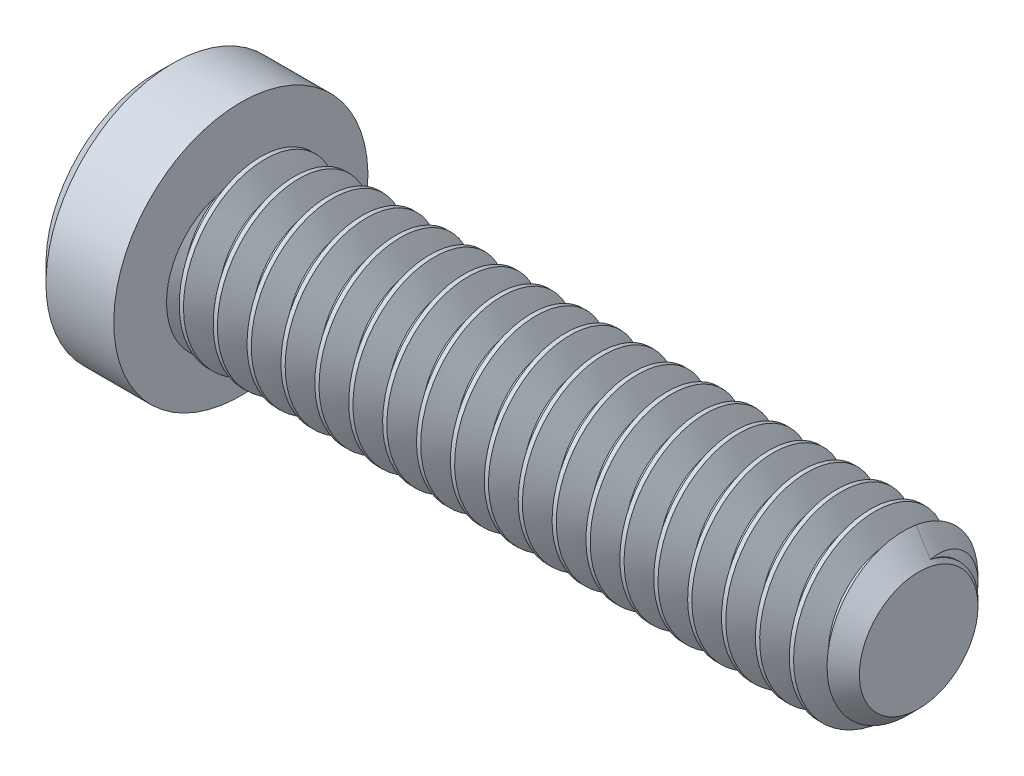
SolidWorks part; units mm, degrees
ref_plane "Front Plane" through (0, 0, 0) normal (0, 0, 1) x (1, 0, 0)
ref_plane "Top Plane" through (0, 0, 0) normal (0, 1, 0) x (1, 0, 0)
ref_plane "Right Plane" through (0, 0, 0) normal (1, 0, 0) x (0, 0, -1)
sketch "Sketch1" plane through (0, 0, 0) normal (0, 0, 1) x (1, 0, 0)
  line L0 (12.7, 0) -> (-12.7, 0) construction
  line L1 (12.7, 3.175) -> (12.7, -3.175) construction
  line L2 (-12.7, 4.7625) -> (-12.7, -4.7625) construction
  line L3 (-12.7, 4.7625) -> (-15.24, 4.7625) construction
  line L4 (-15.24, 4.7625) -> (-15.875, 4.1275) construction
  line L5 (-15.875, 4.1275) -> (-15.875, -4.1275) construction
  line L6 (-15.875, -4.1275) -> (-15.24, -4.7625) construction
  line L7 (-15.24, -4.7625) -> (-12.7, -4.7625) construction
  point P7 (-13.4874, 0)
  point P12 (7.62, -3.175)
  dimension "D1" = 45
  dimension "D2" = 5.08
  dimension "Dec." = 6.35
  dimension "Length" = 25.4
  dimension "Head Dia" = 9.525
  dimension "Head Height" = 3.175
  dimension "Hex Depth" = 2.3876
  dimension "Chamfer" = 0.635
ref_plane "Plane1" through (12.7, 0, 0) normal (1, 0, 0) x (0, 0, -1)
ref_plane "Plane2" through (-15.875, 0, 0) normal (1, 0, 0) x (0, 0, -1)
sketch "Sketch2" plane through (12.7, 0, 0) normal (1, 0, 0) x (0, 0, -1)
  circle A0 centre (0, 0) radius 3.175
extrude "Boss-Extrude1" add sketch "Sketch2" against normal up to vertex (25.4 mm away) up to point (-12.7, 0, 0)
sketch "Sketch3" plane through (12.7, 0, 0) normal (1, 0, 0) x (0, 0, -1)
  circle A0 centre (0, 0) radius 3.175 construction
  circle A1 centre (0, 0) radius 3.175
curve "Helix/Spiral1" pitch 1.27 height 26.67 turns 21 parameters "Pitch"=1.27
chamfer "Chamfer1" distance 0.9525 angle 45 1 edges at (12.7, 0, -3.175)
sketch "Sketch5" plane through (0, 0, 0) normal (0, 0, 1) x (1, 0, 0)
  line L0 (12.1444, 3.175) -> (13.2556, 3.175)
  line L1 (13.2556, 3.175) -> (12.7794, 2.3501)
  line L2 (12.7794, 2.3501) -> (12.6206, 2.3501)
  line L3 (12.6206, 2.3501) -> (12.1444, 3.175)
  line L4 (12.7, 2.3501) -> (12.7, 3.175) construction
  line L5 (12.3825, 2.7626) -> (13.0175, 2.7626) construction
  dimension "D1" = 60
  dimension "D2" = 0.635
  dimension "D3" = 0.1588
sweep "Cut-Sweep1" cut profiles "Sketch5" path "Helix/Spiral1" align with end faces yes
sketch "Sketch4" plane through (-15.875, 0, 0) normal (1, 0, 0) x (0, 0, -1)
  line L0 (-4.7625, 0.7937) -> (4.7625, 0.7937) construction
  line L1 (0, 1.8331) -> (-1.5875, 0.9165)
  line L2 (-1.5875, 0.9165) -> (-1.5875, -0.9165)
  line L3 (-1.5875, -0.9165) -> (0, -1.8331)
  line L4 (0, -1.8331) -> (1.5875, -0.9165)
  line L5 (1.5875, -0.9165) -> (1.5875, 0.9165)
  line L6 (1.5875, 0.9165) -> (0, 1.8331)
  line L7 (0, 0) -> (0, 0.7937) construction
  circle A0 centre (0, 0) radius 1.5875 construction
  dimension "D1" = 9.525
  dimension "Hex Size" = 3.175
  dimension "D2" = 0.7937
sketch "Sketch6" plane through (0, 0, 0) normal (0, 0, 1) x (1, 0, 0)
  line L0 (-15.24, 4.7625) -> (-15.875, 4.1275) construction
  line L1 (-12.7, 4.7625) -> (-15.24, 4.7625) construction
  line L2 (-12.7, 4.7625) -> (-12.7, -4.7625) construction
  line L3 (-15.875, 4.1275) -> (-15.875, -4.1275) construction
  line L4 (-15.24, 4.7625) -> (-15.875, 4.1275)
  line L5 (-12.7, 4.7625) -> (-15.24, 4.7625)
  line L6 (-12.7, 4.7625) -> (-12.7, 0)
  line L7 (-15.875, 4.1275) -> (-15.875, 0)
  line L8 (-12.7, 0) -> (-15.875, 0) construction
  line L9 (-12.7, 0) -> (-15.875, 0)
revolve "Revolve1" add sketch "Sketch6" angle 360 about L8
extrude "Cut-Extrude1" cut sketch "Sketch4" along normal up to vertex (2.3876 mm away) up to point (-13.4874, 0, 0)
sketch "Sketch8" plane through (-15.875, 0, 0) normal (-1, 0, 0) x (0, 0, 1)
  circle A1 centre (0, 0) radius 1.8331
extrude "Cut-Extrude2" cut sketch "Sketch8" against normal through all draft 45
equation "\"D3@Helix/Spiral1\" = \"Length@Sketch1\"+\"Pitch@Helix/Spiral1\""
equation "\"D3@Sketch5\" = \"Pitch@Helix/Spiral1\"*.125"
equation "\"D2@Sketch5\" = \"Pitch@Helix/Spiral1\"*.50"
equation "\"D1@Chamfer1\" = \"Pitch@Helix/Spiral1\"*.75"
equation "\"D2@Sketch1\" = \"Pitch@Helix/Spiral1\"*4"
equation "\"D1@Sketch4\" = \"Head Dia@Sketch1\""
